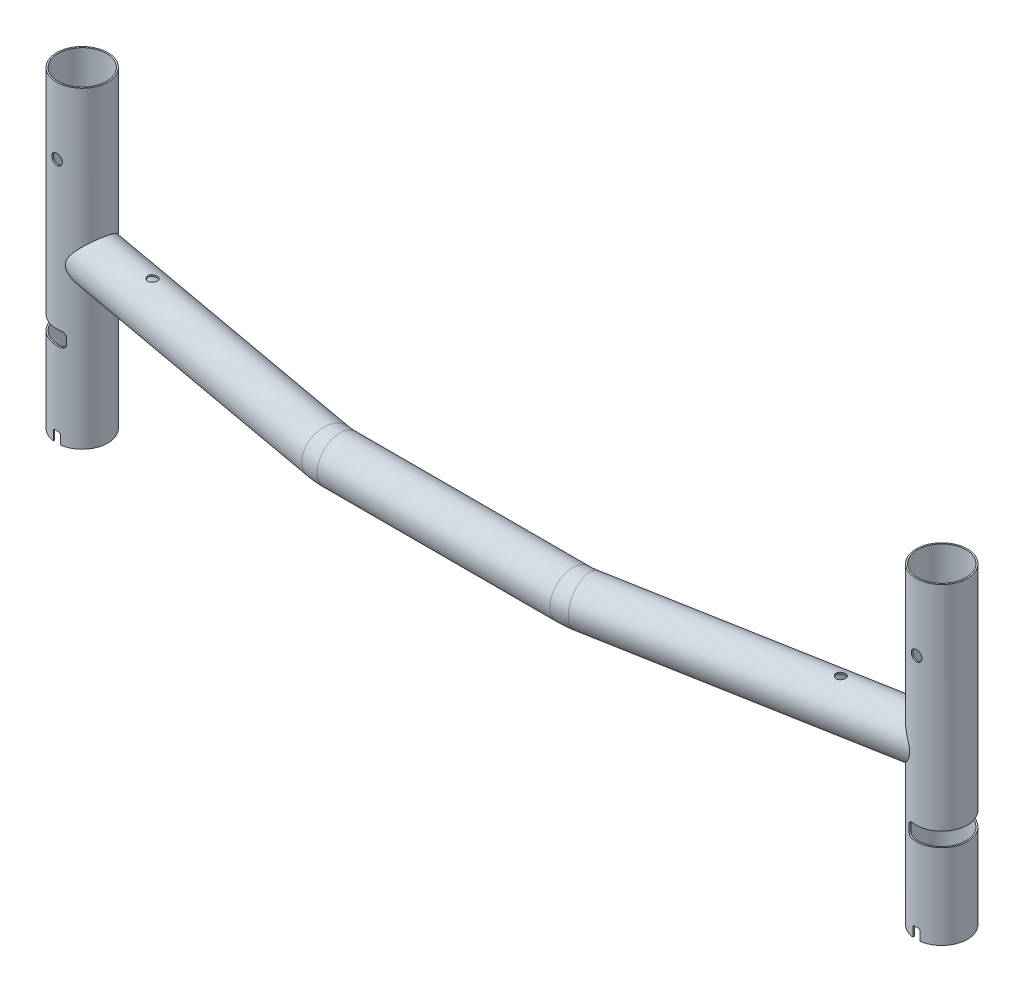
SolidWorks part; units mm, degrees
ref_plane "Front Plane" through (0, 0, 0) normal (0, 0, 1) x (1, 0, 0)
ref_plane "Top Plane" through (0, 0, 0) normal (0, 1, 0) x (1, 0, 0)
ref_plane "Right Plane" through (0, 0, 0) normal (1, 0, 0) x (0, 0, -1)
sketch "Sketch1" plane through (0, 0, 0) normal (0, 1, 0) x (1, 0, 0)
  line L0 (0, 0) -> (0, 107.988) construction
  line L1 (-65, 0) -> (65, 0)
  line L2 (72.1386, 0.6421) -> (234, 30)
  line L3 (-72.1386, 0.6421) -> (-234, 30)
  arc A0 (72.1386, 0.6421) -> (65, 0) centre (65, 40) cw
  arc A1 (-72.1386, 0.6421) -> (-65, 0) centre (-65, 40) ccw
  dimension "D2" = 40
  dimension "D1" = 234
  dimension "D3" = 65
  dimension "D4" = 30
ref_plane "Plane1" through (234, 0, -30) normal (0.9839, 0, -0.1785) x (-0.1785, 0, -0.9839)
sketch "Sketch2" plane through (234, 0, -30) normal (0.9839, 0, -0.1785) x (-0.1785, 0, -0.9839)
  line L0 (0.6421, 0) -> (0, 0) construction
  circle A0 centre (0, 0) radius 12.7
  circle A1 centre (0, 0) radius 11.9
  dimension "D1" = 0.8
  dimension "D2" = 25.4
sweep "Sweep1" add profiles "Sketch2" path "Sketch1"
sketch "Sketch3" plane through (0, 0, 0) normal (0, 1, 0) x (1, 0, 0)
  line L0 (231.7335, 42.4961) -> (236.2665, 17.5039) construction
  line L1 (231.7335, 42.4961) -> (234, 30) construction
  line L2 (234, 30) -> (239.9037, 31.0708) construction
  circle A0 centre (239.9037, 31.0708) radius 14.3
  circle A1 centre (239.9037, 31.0708) radius 13.5
  dimension "D1" = 0.8
  dimension "D3" = 28.6
  dimension "D4" = 0.8
  dimension "D2" = 6
extrude "Boss-Extrude1" add sketch "Sketch3" along normal blind 86.5 and the other way blind 88
sketch "Sketch4" plane through (0, -88, 0) normal (0, -1, 0) x (1, 0, 0)
  circle A0 centre (239.9037, -31.0708) radius 13.5
  dimension "D1" = 27
extrude "Cut-Extrude1" cut sketch "Sketch4" against normal through all
sketch "Sketch5" plane through (234, 0, -30) normal (0.9839, 0, -0.1785) x (-0.1785, 0, -0.9839)
  circle A0 centre (-0.0149, 0) radius 11.9
  dimension "D1" = 23.8
extrude "Cut-Extrude2" cut sketch "Sketch5" against normal blind 88
sketch "Sketch6" plane through (0, 86.5, 0) normal (0, 1, 0) x (1, 0, 0)
  line L0 (239.9037, 31.0708) -> (72.1386, 0.6421)
  line L1 (69.8721, 13.1383) -> (74.4051, -11.854) construction
  line L2 (239.9037, 31.0708) -> (244.4588, 43.7791)
  circle A0 centre (239.9037, 31.0708) radius 13.5 construction
  dimension "D1" = 60
ref_plane "Plane2" through (239.9037, 86.5, -31.0708) normal (0.3374, 0, -0.9414) x (-0.9414, 0, -0.3374)
sketch "Sketch7" plane through (239.9037, 86.5, -31.0708) normal (0.3374, 0, -0.9414) x (-0.9414, 0, -0.3374)
  line L0 (0, -174.5) -> (0, -125.7306) construction
  line L1 (-14.3, -174.5) -> (14.3, -174.5) construction
  line L2 (-12.7, -119.2306) -> (-27.4942, -119.2306)
  line L3 (-27.4942, -119.2306) -> (-27.4942, -127.2306)
  line L4 (-2.5, -119.2306) -> (-12.7, -119.2306)
  line L5 (-2.5, -127.2306) -> (-12.7, -127.2306)
  line L7 (0, -121.7306) -> (0, -124.7306)
  line L8 (-27.4942, -127.2306) -> (-12.7, -127.2306)
  arc A0 (0, -121.7306) -> (-2.5, -119.2306) centre (-2.5, -121.7306) ccw
  arc A1 (0, -124.7306) -> (-2.5, -127.2306) centre (-2.5, -124.7306) cw
  point P12 (0, -123.2306)
  dimension "D1" = 2.5
  dimension "D2" = 51.2694
extrude "Cut-Extrude3" cut sketch "Sketch7" against normal blind 20 and the other way blind 20
sketch "Sketch9" plane through (0, 0, 0) normal (0, 0, 1) x (1, 0, 0)
  line L0 (225.6037, -88) -> (254.2037, -88) construction
  line L1 (238.9037, -82) -> (240.9037, -82)
  line L2 (237.9037, -83) -> (237.9037, -94)
  line L3 (237.9037, -94) -> (241.9037, -94)
  line L4 (241.9037, -83) -> (241.9037, -94)
  line L5 (237.9037, -82) -> (241.9037, -94) construction
  line L6 (237.9037, -94) -> (241.9037, -82) construction
  arc A0 (241.9037, -83) -> (240.9037, -82) centre (240.9037, -83) ccw
  arc A1 (238.9037, -82) -> (237.9037, -83) centre (238.9037, -83) ccw
  point P0 (239.9037, -88)
  dimension "D3" = 1
  dimension "D1" = 12
  dimension "D2" = 4
extrude "Cut-Extrude5" cut sketch "Sketch9" against normal up to surface (17.7198 mm away) up to face at (239.9037, -88, -17.5708)
mirror "Mirror1" about plane through (0, 0, 0) normal (1, 0, 0) of "Cut-Extrude5", "Cut-Extrude2", "Cut-Extrude3", "Boss-Extrude1", "Cut-Extrude1"
sketch "Sketch8" plane through (0, 0, 0) normal (0, 1, 0) x (1, 0, 0)
  line L0 (72.1386, 0.6421) -> (216.9875, 26.5937) construction
  line L1 (69.8721, 13.1383) -> (74.4051, -11.854) construction
  circle A0 centre (216.9875, 26.5937) radius 3
extrude "Cut-Extrude4" cut sketch "Sketch8" against normal up to next
sketch "Sketch10" plane through (0, 0, 0) normal (0, 0, 1) x (1, 0, 0)
  line L0 (0, 0) -> (0, 80.0817) construction
  line L1 (-239.9037, -40.8) -> (-239.9037, 49.2) construction
  line L2 (-225.6037, 86.5) -> (-254.2037, 86.5) construction
  circle A0 centre (-239.9037, 49.2) radius 2.95
  dimension "D1" = 37.3
  dimension "D2" = 5.9
extrude "Cut-Extrude6" cut sketch "Sketch10" against normal through all and the other way through all
sketch "Sketch11" plane through (0, 0, 0) normal (0, 1, 0) x (1, 0, 0)
  line L0 (239.9037, 31.0708) -> (65, 0) construction
  line L1 (65, 12.7) -> (65, -12.7) construction
  line L2 (65, 0) -> (-65, 0) construction
  line L3 (-65, 12.7) -> (-65, -12.7) construction
  line L4 (-65, 0) -> (-239.9037, 31.0708) construction
  line L5 (0, 0) -> (0, 65.6963) construction
  circle A0 centre (192.0842, 22.5759) radius 2.6
  circle A1 centre (-192.0842, 22.5759) radius 2.6
extrude "Cut-Extrude7" cut sketch "Sketch11" along normal through all and the other way through all
mirror "Mirror2" about plane through (0, 0, 0) normal (1, 0, 0) of "Cut-Extrude6"
